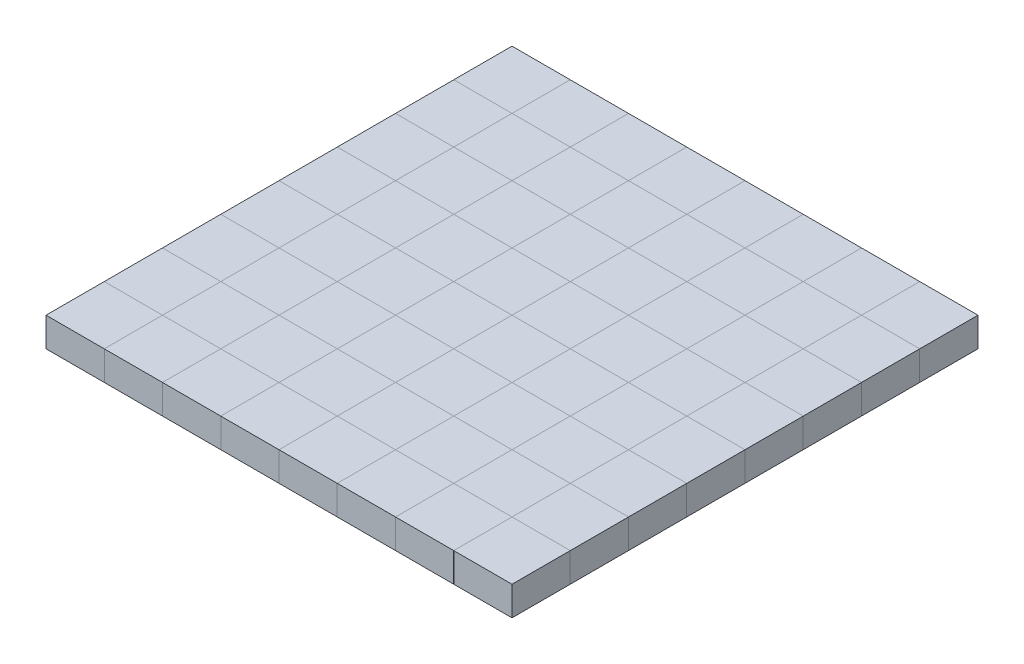
SolidWorks part; units mm, degrees
ref_plane "Front Plane" through (0, 0, 0) normal (0, 0, 1) x (1, 0, 0)
ref_plane "Top Plane" through (0, 0, 0) normal (0, 1, 0) x (1, 0, 0)
ref_plane "Right Plane" through (0, 0, 0) normal (1, 0, 0) x (0, 0, -1)
sketch "Sketch1" plane through (0, 0, 0) normal (0, 1, 0) x (1, 0, 0)
  line L1 (-20, 20) -> (20, 20)
  line L2 (-20, 20) -> (-20, -20)
  line L3 (-20, -20) -> (20, -20)
  line L4 (20, 20) -> (20, -20)
  line L5 (-20, 20) -> (20, -20) construction
  line L6 (-20, -20) -> (20, 20) construction
  point P0 (0, 0)
  dimension "D1" = 40
  dimension "D2" = 40
extrude "Boss-Extrude1" add sketch "Sketch1" along normal blind 20
sketch "Sketch2" plane through (0, 0, 0) normal (0, 1, 0) x (1, 0, 0)
  line L1 (-20, 20) -> (20, 20)
  line L2 (-20, 20) -> (-20, 60)
  line L3 (-20, 60) -> (20, 60)
  line L4 (20, 20) -> (20, 60)
  dimension "D1" = 40
extrude "Boss-Extrude2" add sketch "Sketch2" along normal blind 20 separate body
sketch "Sketch3" plane through (0, 0, 0) normal (0, 1, 0) x (1, 0, 0)
  line L0 (-20, -20) -> (20, -20) construction
  line L1 (20, 60) -> (60, 60)
  line L2 (20, 60) -> (20, -20)
  line L3 (20, -20) -> (60, -20)
  line L4 (60, 60) -> (60, -20)
  line L5 (20, 20) -> (60, 20)
  line L6 (20, 20) -> (-20, 20) construction
  dimension "D1" = 40
extrude "Boss-Extrude4" add sketch "Sketch3" along normal blind 20 separate body contours L5 L2 L3 L4 region at (40, 0, 0)
extrude "Boss-Extrude5" add sketch "Sketch3<4>" along normal blind 20 separate body contours L2 L5 L4 L1 region at (40, 0, -40)
sketch "Sketch3<4>" plane through (0, 0, 0) normal (0, 1, 0) x (1, 0, 0) same geometry as "Sketch3"
pattern_linear "LPattern1" count 4 spacing 80 along (1, 0, 0) count 4 spacing 80 along (0, 0, -1) of bodies 105 102 104 101
